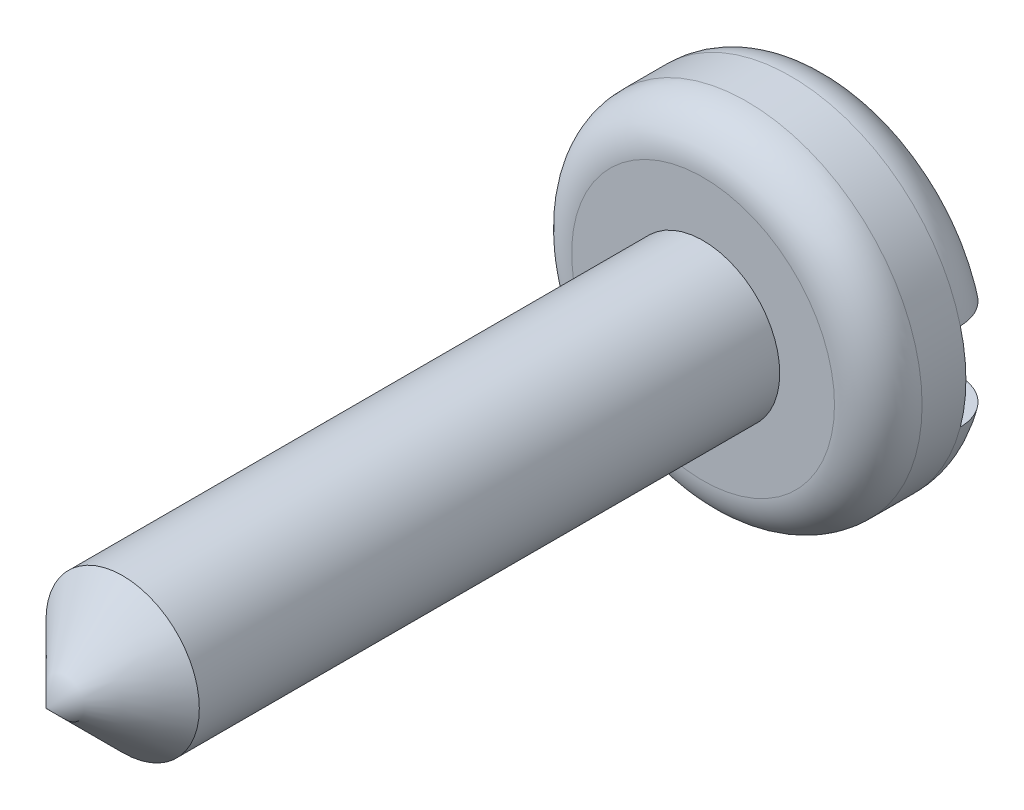
SolidWorks part; units mm, degrees
ref_plane "Front Plane" through (0, 0, 0) normal (0, 0, 1) x (1, 0, 0)
ref_plane "Top Plane" through (0, 0, 0) normal (0, 1, 0) x (1, 0, 0)
ref_plane "Right Plane" through (0, 0, 0) normal (1, 0, 0) x (0, 0, -1)
sketch "Sketch1" plane through (0, 0, 0) normal (0, 0, 1) x (1, 0, 0)
  circle A0 centre (0, 0) radius 4
  dimension "D1" = 8
extrude "Boss-Extrude1" add sketch "Sketch1" along normal blind 3
sketch "Sketch2" plane through (0, 0, 3) normal (0, 0, 1) x (1, 0, 0)
  circle A0 centre (0, 0) radius 1.75
  dimension "D1" = 3.5
extrude "Boss-Extrude2" add sketch "Sketch2" along normal blind 15
fillet "Fillet2" radius 1 2 edges at (4, 0, 0) (4, 0, 3)
sketch "Sketch3" plane through (0, 0, 0) normal (0, 0, -1) x (-1, 0, 0)
  line L0 (-6.1717, 0) -> (5.7671, 0) construction
  line L1 (-6.1717, -1) -> (5.7671, -1)
  line L2 (-6.1717, -1) -> (-6.1717, 1)
  line L3 (-6.1717, 1) -> (5.7671, 1)
  line L4 (5.7671, -1) -> (5.7671, 1)
  dimension "D1" = 2
extrude "Cut-Extrude1" cut sketch "Sketch3" against normal blind 1
ref_axis "Axis1" through (0, 0, 18) along (0, 0, -1)
chamfer "Chamfer1" distance 1.75 angle 45 1 edges at (1.75, 0, 18)
equation "\"D1@Chamfer1\"=3.5/2"
